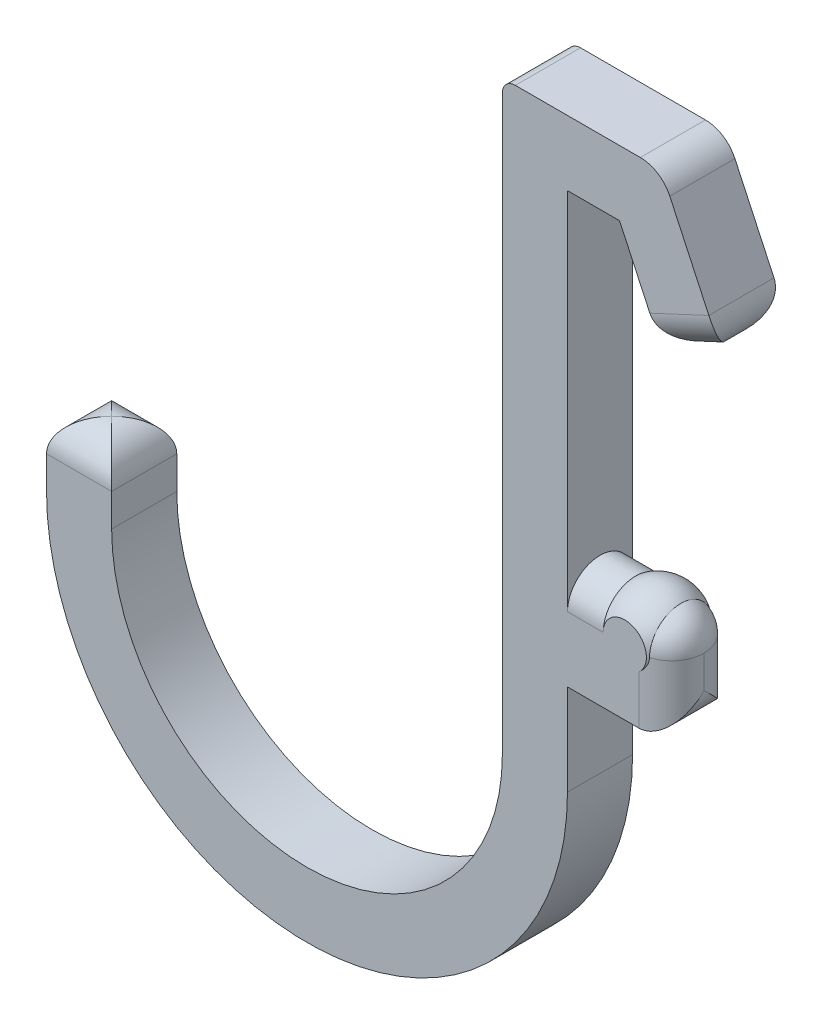
SolidWorks part; units mm, degrees
ref_plane "前视基准面" through (0, 0, 0) normal (0, 0, 1) x (1, 0, 0)
ref_plane "上视基准面" through (0, 0, 0) normal (0, 1, 0) x (1, 0, 0)
ref_plane "右视基准面" through (0, 0, 0) normal (1, 0, 0) x (0, 0, -1)
sketch "草图1" plane through (0, 0, 0) normal (0, 0, 1) x (1, 0, 0)
  line L0 (0, 0) -> (0, 28)
  line L1 (0, 28) -> (4, 28)
  line L2 (4, 28) -> (7.3809, 20.7495)
  line L3 (0, 0) -> (8, 0)
  line L4 (8, 0) -> (8, -5)
  line L5 (8, -5) -> (0, -5)
  line L6 (7.3809, 20.7495) -> (11.9125, 22.8626)
  line L7 (11.9125, 22.8626) -> (7.1854, 33)
  line L8 (-5, 33) -> (7.1854, 33)
  line L9 (-5, 33) -> (-5, -12)
  line L10 (-35, -12) -> (-5, -12) construction
  line L11 (-35, -12) -> (-35, -7)
  line L12 (-35, -7) -> (-40, -7)
  line L13 (-40, -7) -> (-40, -12)
  line L14 (0, -5) -> (0, -12)
  arc A0 (-35, -12) -> (-5, -12) centre (-20, -12) ccw
  arc A1 (-40, -12) -> (0, -12) centre (-20, -12) ccw
  dimension "D11" = 15
  dimension "D1" = 4
  dimension "D2" = 65
  dimension "D3" = 28
  dimension "D4" = 8
  dimension "D5" = 5
  dimension "D6" = 5
  dimension "D7" = 5
  dimension "D8" = 45
  dimension "D9" = 5
  dimension "D10" = 8
  dimension "D12" = 5
  dimension "D13" = 5
extrude "凸台-拉伸1" add sketch "草图1" along normal blind 5
fillet "圆角1" radius 2.5 9 edges at (7.3809, 20.7495, 2.5) (9.6467, 21.8061, 5) (11.9125, 22.8626, 2.5) (9.6467, 21.8061, 0) (-35, -7, 2.5) (-37.5, -7, 5) (-40, -7, 2.5) (-37.5, -7, 0) (7.1854, 33, 2.5)
fillet "圆角2" radius 1 1 edges at (-5, 33, 2.5)
sketch "草图3" plane through (0, 0, 0) normal (1, 0, 0) x (0, 0, -1)
  line L0 (-5, 0) -> (0, 0) construction
  line L1 (-5, 0) -> (0, 0)
  arc A0 (0, 0) -> (-5, 0) centre (-2.5, 0) ccw
extrude "凸台-拉伸2" add sketch "草图3" along normal up to surface (8 mm away) up to face at (8, -2.5, 2.5)
fillet "圆角3" radius 2.5 4 edges at (8, -2.5, 5) (8, -2.5, 0) (8, -5, 2.5) (8, 2.5, 2.5)
ref_plane "基准面1" through (4.4, 0, 0) normal (1, 0, 0) x (0, 0, -1)
sketch "草图4" plane through (4.4, 0, 0) normal (1, 0, 0) x (0, 0, -1)
  line L0 (-2.5, 0) -> (0.5, 0) construction
  line L1 (-5.5, 0) -> (0.5, 0)
  arc A0 (0.5, 0) -> (-5.5, 0) centre (-2.5, 0) ccw
revolve "旋转3" add sketch "草图4" angle 360 about L0
sketch "草图5" plane through (-5, 0, 0) normal (-1, 0, 0) x (0, 0, 1)
  line L0 (0, -2.0992) -> (-1.4678, -2.0992)
  line L1 (0, 32) -> (0, -12) construction
  line L2 (-1.4678, -2.0992) -> (-1.4678, 2.0791)
  line L3 (-1.4678, 2.0791) -> (0, 2.0791)
  line L4 (0, 2.0791) -> (0, -2.0992)
  line L5 (5, -2.0992) -> (6.3896, -2.0992)
  line L6 (5, 32) -> (5, -12) construction
  line L7 (6.3896, -2.0992) -> (6.3896, 2.0791)
  line L8 (6.3896, 2.0791) -> (5, 2.0791)
  line L9 (5, 2.0791) -> (5, -2.0992)
extrude "切除-拉伸1" cut sketch "草图5" against normal blind 20
